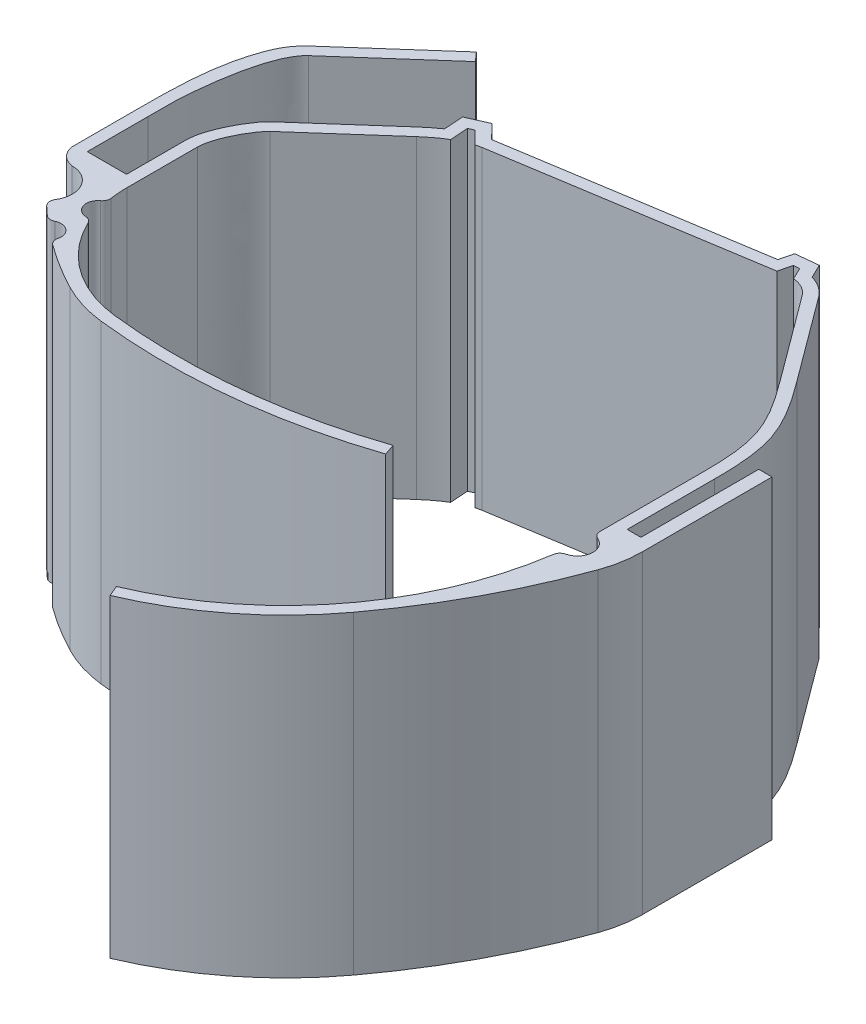
SolidWorks part; units mm, degrees
ref_plane "Front Plane" through (0, 0, 0) normal (0, 0, 1) x (1, 0, 0)
ref_plane "Top Plane" through (0, 0, 0) normal (0, 1, 0) x (1, 0, 0)
ref_plane "Right Plane" through (0, 0, 0) normal (1, 0, 0) x (0, 0, -1)
sketch "Sketch1" plane through (0, 0, 0) normal (0, 1, 0) x (1, 0, 0)
  line L0 (0, 0) -> (0, 15.0499) construction
  line L1 (0, 15.0499) -> (19.1847, 32) construction
  line L2 (19.1847, 32) -> (52.7654, 37.3233) construction
  line L3 (52.7654, 37.3233) -> (73, 10) construction
  line L4 (73, 10) -> (73, -10) construction
  line L5 (20.3981, 24.3456) -> (53.9788, 29.6689)
  line L6 (4.4137, 12.2775) -> (14.2887, 21.0023)
  line L7 (73, -10) -> (73, -11) construction
  line L9 (-0.0796, 25.8478) -> (9.0646, 33.9269) construction
  line L10 (0, 0) -> (1, 0) construction
  line L12 (73, -10) -> (72, -10) construction
  line L13 (57.2965, 29.5246) -> (71, 11.0204) construction
  line L14 (58.5838, 27.7863) -> (66.4864, 17.1152)
  line L15 (20.3981, 24.3456) -> (19.1847, 32) construction
  line L16 (52.7654, 37.3233) -> (53.9788, 29.6689) construction
  line L17 (1, 0) -> (1, 4.7822)
  line L24 (72, -10) -> (72, 1.1148)
  line L25 (2.5, 0) -> (2.5, 4.7822)
  line L26 (5.4069, 11.1534) -> (15.2819, 19.8782)
  line L27 (20.633, 22.8641) -> (54.2137, 28.1874)
  line L28 (57.3783, 26.8936) -> (65.281, 16.2225)
  line L29 (70.5, -10) -> (70.5, 1.1148)
  line L30 (1, 0) -> (2.5, 0) construction
  line L31 (70.5, -10) -> (72, -10)
  line L32 (1, 0) -> (1, -2.7178)
  line L33 (1, -2.7178) -> (2.5, -2.7178)
  line L34 (2.5, -2.7178) -> (2.5, 0)
  arc A2 (53.9788, 29.6689) -> (58.5838, 27.7863) centre (54.7297, 24.9321) cw
  arc A5 (54.2137, 28.1874) -> (57.3783, 26.8936) centre (54.7297, 24.9321) cw
  spline S0 degree 3 poles (1, 4.7822) (1, 7.4141) (3.1929, 11.1989) (4.4137, 12.2775) knots 0 0 0 0 1 1 1 1
  spline S1 degree 3 poles (66.4864, 17.1152) (68.1767, 14.8327) (71.7768, 9.7993) (72, 3.8973) (72, 1.1148) knots 0 0 0 0 0.517915 1 1 1 1
  spline S2 degree 3 poles (14.2887, 21.0023) (15.2766, 21.8751) (17.2444, 23.3609) (19.4454, 24.1945) (20.3981, 24.3456) knots 0 0 0 0 0.592259 1 1 1 1
  spline S3 degree 1 poles (2.5, 4.7822) (5.4069, 11.1534) knots 0 0 1 1 construction
  spline S4 degree 1 poles (15.2819, 19.8782) (20.633, 22.8641) knots 0 0 1 1 construction
  spline S5 degree 1 poles (65.281, 16.2225) (70.5, 1.1148) knots 0 0 1 1 construction
  spline S6 degree 3 poles (2.5, 4.7822) (2.5, 4.9039) (2.5118, 5.1347) (2.5866, 5.6922) (2.7757, 6.4659) (3.1323, 7.4621) (3.5832, 8.4549) (4.0887, 9.3865) (4.608, 10.2013) (5.0036, 10.7261) (5.2765, 11.0306) (5.3564, 11.1088) (5.4069, 11.1534) knots 0 0 0 0 0.0625 0.125 0.25 0.375 0.5 0.625 0.75 0.875 0.9375 1 1 1 1
  spline S7 degree 3 poles (15.2819, 19.8782) (15.6825, 20.2322) (16.5022, 20.9062) (17.8677, 21.8305) (19.264, 22.5302) (20.1621, 22.7894) (20.633, 22.8641) knots 0 0 0 0 0.25 0.5 0.75 1 1 1 1
  spline S8 degree 3 poles (65.281, 16.2225) (65.6923, 15.6671) (66.5048, 14.5593) (67.6862, 12.8074) (68.7226, 11.0059) (69.5354, 9.177) (70.0552, 7.307) (70.3554, 5.3116) (70.4856, 3.2443) (70.5, 1.8209) (70.5, 1.1148) knots 0 0 0 0 0.125 0.25 0.375 0.5 0.625 0.75 0.875 1 1 1 1
  point P38 (2.5, -5.23)
  dimension "D15" = 1.5
  dimension "D1" = 73
  dimension "D2" = 25.6
  dimension "D3" = 10
  dimension "D4" = 15.0499
  dimension "D5" = 32
  dimension "D6" = 34
  dimension "D7" = 34
  dimension "D8" = 20
  dimension "D9" = 7.75
  dimension "D10" = 5
  dimension "D11" = 1
  dimension "D12" = 1
  dimension "D13" = 34
  dimension "D14" = 1
  dimension "D16" = 7.5
extrude "Boss-Extrude1" add sketch "Sketch1" along normal blind 40 contours L14 S1 L24 L31 L29 S8 L28 A5 L27 S7 L26 S6 L25 L34 L33 L32 L17 S0 L6 S2 L5 A2
sketch "Sketch3" plane through (0, 40, 0) normal (0, 1, 0) x (1, 0, 0)
  line L0 (20.3981, 24.3456) -> (18.6612, 26.1437)
  line L1 (18.6612, 26.1437) -> (16.0572, 24.9839)
  line L2 (16.0572, 24.9839) -> (16.2295, 22.5244)
  line L3 (17.788, 21.7427) -> (17.627, 24.041)
  line L4 (17.627, 24.041) -> (18.3121, 24.3461)
  line L5 (18.3121, 24.3461) -> (19.9016, 22.7005)
  line L6 (17.788, 21.7427) -> (16.2295, 22.5244)
  line L7 (19.9016, 22.7005) -> (20.3981, 24.3456)
  line L8 (20.3981, 24.3456) -> (53.9788, 29.6689) construction
  line L9 (53.0598, 28.0044) -> (53.4755, 29.6663)
  line L10 (53.4755, 29.6663) -> (54.2215, 29.7441)
  line L11 (54.2215, 29.7441) -> (54.9635, 28.2197)
  line L12 (53.0598, 28.0044) -> (51.6685, 28.624)
  line L13 (51.6685, 28.624) -> (52.2753, 31.0492)
  line L14 (52.2753, 31.0492) -> (55.1105, 31.345)
  line L15 (55.1105, 31.345) -> (55.978, 29.5627)
  line L16 (55.978, 29.5627) -> (54.9635, 28.2197)
  line L17 (20.633, 22.8641) -> (54.2137, 28.1874) construction
  line L19 (53.0598, 28.0044) -> (54.2137, 28.1874)
  arc A0 (57.3783, 26.8936) -> (54.2137, 28.1874) centre (54.7297, 24.9321) ccw construction
  arc A1 (58.5838, 27.7863) -> (53.9788, 29.6689) centre (54.7297, 24.9321) ccw construction
  arc A3 (54.9635, 28.2197) -> (54.2137, 28.1874) centre (54.7297, 24.9321) ccw
  spline S0 degree 3 poles (14.2887, 21.0023) (15.2766, 21.8751) (17.2444, 23.3609) (19.4454, 24.1945) (20.3981, 24.3456) knots 0 0 0 0 0.592259 1 1 1 1 construction
  spline S2 degree 3 poles (-1906.0985, -531.6564) (34.9161, -54.7483) (-7.3344, 4.7722) (17.8677, 21.8305) (37.4832, 31.6607) (42.7734, -46.4723) (1972.6455, -409.6403) knots -13.092319 -13.092319 -13.092319 -13.092319 0.25 0.5 0.75 10.786069 10.786069 10.786069 10.786069 only from (15.2819, 19.8782) to (20.633, 22.8641) construction
  spline S3 degree 3 poles (17.788, 21.7427) (17.8162, 21.7596) (18.3045, 22.0494) (19.0185, 22.4072) (19.6861, 22.6383) (19.9016, 22.7005) knots 0.484623 0.484623 0.484623 0.484623 0.5 0.75 0.86812 0.86812 0.86812 0.86812
  point P17 (53.4313, 27.5571)
  point P19 (52.6044, 31.1807)
  point P20 (53.0298, 30.457)
  point P30 (55.4832, 30.541)
  point P31 (53.5243, 30.6998)
  point P32 (0, 0)
  point P33 (56.6523, 30.4741)
  point P34 (52.391, 30.3089)
  point P35 (56.0356, 30.7009)
  point P36 (54.6108, 29.1023)
  point P37 (55.413, 27.6432)
  point P41 (18.6612, 26.1437)
  point P42 (51.7734, 28.7085)
  point P43 (52.4308, 31.031)
  point P44 (51.5223, 28.4977)
  point P45 (52.8692, 31.3366)
  point P46 (51.8744, 28.7854)
  point P47 (52.8028, 31.126)
  point P48 (55.4731, 31.2834)
  point P49 (55.3997, 31.4064)
  point P50 (52.4996, 31.0657)
  point P51 (53.4755, 29.6663)
  point P52 (0, 0)
  arc M27 (58.5838, 27.7863) -> (53.9788, 29.6689) centre (54.7297, 24.9321) ccw
  spline M29 degree 3 poles (20.3981, 24.3456) (19.4454, 24.1945) (17.2444, 23.3609) (15.2766, 21.8751) (14.2887, 21.0023) knots 0 0 0 0 0.407741 1 1 1 1
  dimension "D1" = 1.5
  dimension "D2" = 1.5
  dimension "D3" = 1.5
  dimension "D4" = 250
  dimension "D5" = 250
  dimension "D6" = 165
  dimension "D7" = 1.5
  dimension "D8" = 1.5
  dimension "D9" = 1.5
  dimension "D10" = 250
  dimension "D12" = 250
  dimension "D13" = 0.75
  dimension "D14" = 0.75
  dimension "D15" = 2.5
  dimension "D16" = 2.5
extrude "Boss-Extrude2" add sketch "Sketch3" against normal up to surface (40 mm away) contours L16 L11 M27 | L15 L14 L13 L9 L10 L11 M27 | L12 L9 M27 | L5 L7 M29 | L4 L5 L0 L1 L2 L3 M29 | L6 L3 M29 region at (17.8105, 40, -24.5493) region at (19.6793, 40, -23.6658) region at (17.2238, 40, -22.5639) region at (53.5083, 40, -29.9936) region at (55.0646, 40, -29.1969) up to face at (35.7266, 0, -12.5148)
extrude "Cut-Extrude2" cut sketch "Sketch3<4>" against normal through all contours L5 L3 M29 | L11 L9 M27 region at (18.5483, 40, -22.8866) region at (53.9347, 40, -28.8112)
sketch "Sketch3<4>" plane through (0, 40, 0) normal (0, 1, 0) x (1, 0, 0) same geometry as "Sketch3"
sketch "Sketch6" plane through (0, 40, 0) normal (0, 1, 0) x (1, 0, 0)
  line L0 (-0.5046, 21.9433) -> (10.772, 31.9064)
  line L1 (2.5, -2.7178) -> (-5.5, -2.7178)
  line L2 (2.5, -2.7178) -> (2.5, -4.1706)
  line L3 (2.5, -4.1706) -> (-5.5, -4.1706)
  line L4 (-5.5, -2.7178) -> (-5.5, -4.1706)
  line L5 (-5.5, -2.7178) -> (-4, -2.7178)
  line L6 (-5.5, -2.7178) -> (-5.5, 5.0044)
  line L7 (-5.5, 5.0044) -> (-4, 5.0044)
  line L8 (-4, -2.7178) -> (-4, 5.0044)
  line L9 (4.4137, 12.2775) -> (14.2887, 21.0023) construction
  line L10 (1, 4.7822) -> (1, -2.7178) construction
  line L11 (10.772, 31.9064) -> (9.7788, 33.0305)
  line L12 (9.7788, 33.0305) -> (-1.4977, 23.0674)
  line L13 (-1.4977, 23.0674) -> (-0.5046, 21.9433) construction
  line L14 (-2.5624, 22.1267) -> (-0.3755, 24.0589) construction
  line L15 (72, -10) -> (72, 1.1148) construction
  line L16 (70.5, -10) -> (73.75, -10)
  line L17 (70.5, -10) -> (70.5, -11.5)
  line L18 (70.5, -11.5) -> (73.75, -11.5)
  line L19 (73.75, -10) -> (73.75, -11.5)
  line L21 (73.75, -11.5) -> (75.438, -11.5)
  line L22 (73.75, -11.5) -> (73.75, 5)
  line L23 (73.75, 5) -> (75.438, 5)
  line L24 (75.438, -11.5) -> (75.438, 5)
  spline S0 degree 3 poles (-4, 5.0044) (-4, 7.1489) (-4.1506, 9.8422) (-2.6282, 20.067) (-0.5046, 21.9433) knots 0 0 0 0 0.427266 1 1 1 1
  spline S1 degree 3 poles (-1.4977, 23.0674) (-2.8646, 21.8598) (-5.3843, 16.169) (-5.5, 10.323) (-5.5, 5.0044) knots 0 0 0 0 0.256758 1 1 1 1
  line M22 (70.5, -10) -> (72, -10)
  line M38 (1, -2.7178) -> (2.5, -2.7178)
  dimension "D4" = 1.75
  dimension "D1" = 10.5
  dimension "D2" = 5
  dimension "D3" = 1.5
  dimension "D5" = 1.5
  dimension "D6" = 15
extrude "Boss-Extrude3" add sketch "Sketch6" against normal up to surface (40 mm away) contours L12 S1 L7 L0 L11 | L1 L8 L7 L6 | L1 L4 L3 L2 M38 | L19 L16 L17 L18 M22 | L21 L24 L23 L22 L19 region at (-3.7784, 40, -13.8346) region at (-4.75, 40, -1.1433) region at (-1.5, 40, 3.4442) region at (72.125, 40, 10.75) region at (74.594, 40, 3.25) up to face at (35.2981, 0, -18.0798)
sketch "Sketch7" plane through (0, 40, 0) normal (0, 1, 0) x (1, 0, 0)
  line L0 (2.5, -4.1706) -> (2.5, 4.7822) construction
  line L1 (70.5, -11.5) -> (70.5, 1.1148) construction
  line L2 (1, -4.1706) -> (2.5, -4.1706)
  line L3 (48.3238, -17.0562) -> (47.8436, -15.6352)
  line L4 (70.5, -11.5) -> (72, -11.5)
  line L5 (45.7918, -48.803) -> (46.377, -50.1841)
  line L6 (-5.5, -4.1706) -> (-5.5, 5.0044) construction
  line L7 (-5.5, -4.1706) -> (1, -4.1706)
  line L8 (75.438, -11.5) -> (75.438, 5) construction
  arc A0 (2.5, -4.1706) -> (15.7484, -19.0348) centre (17.4627, -4.1706) ccw
  arc A1 (70.5, -11.5) -> (45.7918, -48.803) centre (29.987, -11.5) cw
  arc A2 (15.7484, -19.0348) -> (47.8436, -15.6352) centre (24.2072, 54.309) ccw
  arc A3 (1, -4.1706) -> (15.5766, -20.5249) centre (17.4627, -4.1706) ccw
  arc A4 (15.5766, -20.5249) -> (48.3238, -17.0562) centre (24.2072, 54.309) ccw
  arc A5 (72, -11.5) -> (46.377, -50.1841) centre (29.987, -11.5) cw
  arc A6 (72, -11.5) -> (46.377, -50.1841) centre (29.987, -11.5) cw construction
  arc A7 (-5.5, -4.1706) -> (-4.4761, -7.0649) centre (-0.8973, -4.1706) ccw
  arc A8 (-4.4761, -7.0649) -> (9.8865, -18.7864) centre (30.7151, 21.3955) ccw
  arc A9 (75.438, -11.5) -> (74.5982, -16.2895) centre (61.3598, -11.5) cw
  arc A10 (63.7203, -36.5432) -> (74.5982, -16.2895) centre (0.1648, 10.6396) ccw
  line M35 (-5.5, -4.1706) -> (2.5, -4.1706)
  line M59 (70.5, -11.5) -> (75.438, -11.5)
  dimension "D1" = 1.5
  dimension "D2" = 1.5
extrude "Boss-Extrude4" add sketch "Sketch7" against normal up to surface (40 mm away) contours A7 A8 A3 M35 | A3 A4 L3 A2 A0 M35 | A5 A1 L5 | A5 A10 A9 M59 region at (-0.3581, 40, 8.6295) region at (1.75, 40, 4.6729) region at (71.25, 40, 11.9673) region at (72.3227, 40, 18.3145) up to face at (32.5115, 0, -15.4624)
sketch "Sketch8" plane through (0, 40, 0) normal (0, 1, 0) x (1, 0, 0)
  line L0 (-5.5, -4.1706) -> (-5.5, 5.0044) construction
  line L1 (-5.5, -4.1706) -> (-5.5, -2.5102)
  arc A0 (3.4325, -14.7165) -> (1.1166, -12.8441) centre (2.2592, -13.7994) ccw
  arc A1 (-4.4761, -7.0649) -> (9.8865, -18.7864) centre (30.7151, 21.3955) ccw construction
  arc A2 (2.7767, -7.0348) -> (3.6336, -9.8836) centre (3.1342, -8.4805) ccw
  arc A3 (2.5, -4.1706) -> (15.7484, -19.0348) centre (17.4627, -4.1706) ccw construction
  arc A4 (-1.2545, -10.6414) -> (-3.3823, -5.2517) centre (-3.3823, -8.3666) ccw
  arc A5 (-3.3823, -5.2517) -> (-5.5, -2.5102) centre (-3.0704, -2.8221) cw
  arc A9 (1.1166, -12.8441) -> (3.4325, -14.7165) centre (30.7151, 21.3955) ccw
  arc A10 (-5.5, -4.1706) -> (-4.4761, -7.0649) centre (-0.8973, -4.1706) ccw construction
  arc A11 (2.7767, -7.0348) -> (3.6336, -9.8836) centre (17.4627, -4.1706) ccw
  arc A12 (-4.4761, -7.0649) -> (-1.2545, -10.6414) centre (30.7151, 21.3955) ccw
  arc A13 (-5.5, -4.1706) -> (-4.4761, -7.0649) centre (-0.8973, -4.1706) ccw
  point P1 (2.2592, -13.7994)
  point P16 (0, 0)
extrude "Cut-Extrude3" cut sketch "Sketch8" against normal through all contours L1 A13 A12 A4 A5 | A11 A2 | A0 A9 region at (-2.5955, 40, 7.2494) region at (2.6593, 40, 13.3044) region at (2.5418, 40, 8.6587)
sketch "Sketch9" plane through (0, 40, 0) normal (0, 1, 0) x (1, 0, 0)
  circle A0 centre (70.3733, -14.702) radius 1.979
  arc A1 (45.7918, -48.803) -> (70.5, -11.5) centre (29.987, -11.5) ccw construction
extrude "Cut-Extrude4" cut sketch "Sketch9" against normal through all contours A0
fillet "Fillet1" radius 1 7 edges at (-1.2545, 20, 10.6414) (3.4325, 20, 14.7165) (1.1166, 20, 12.8441) (3.6336, 20, 9.8836) (2.7767, 20, 7.0348) (70.1687, 20, 16.6703) (70.4814, 20, 12.726)
